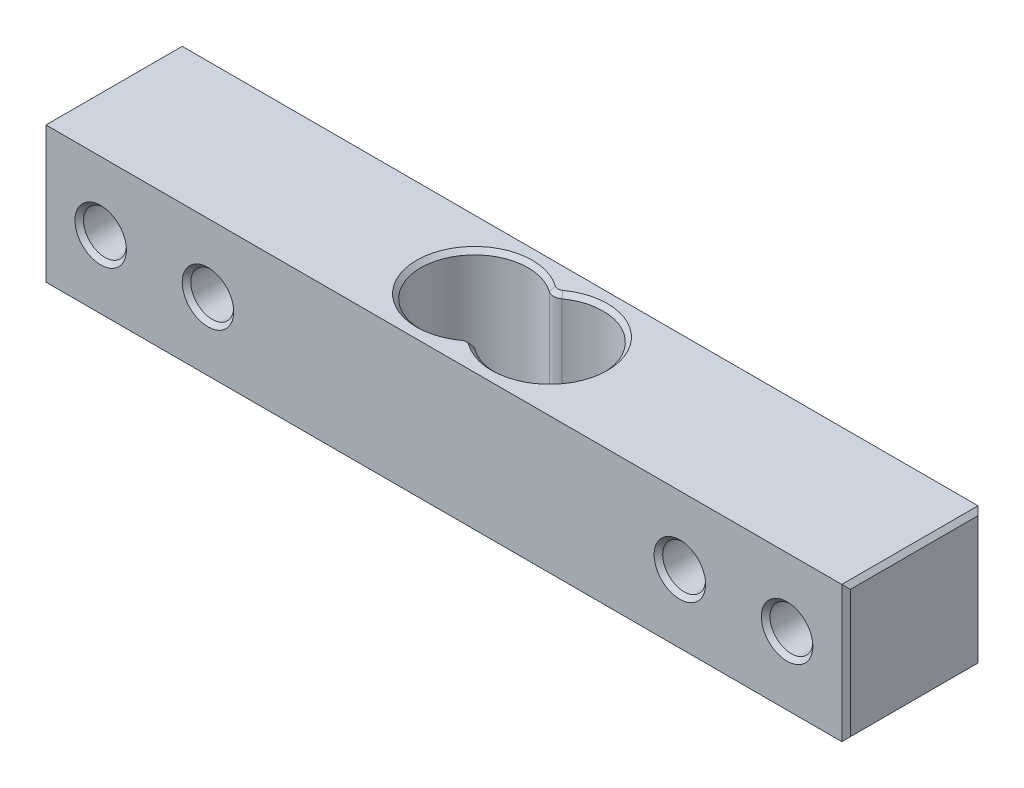
SolidWorks part; units mm, degrees
material "1060 Alloy"
ref_plane "Front Plane" through (0, 0, 0) normal (0, 0, 1) x (1, 0, 0)
ref_plane "Top Plane" through (0, 0, 0) normal (0, 1, 0) x (1, 0, 0)
ref_plane "Right Plane" through (0, 0, 0) normal (1, 0, 0) x (0, 0, -1)
sketch "Sketch1" plane through (0, 0, 0) normal (0, 0, 1) x (1, 0, 0)
  line L0 (-22, 0) -> (22, 0) construction
  line L1 (-37.5, -6.35) -> (37.5, -6.35)
  line L2 (-37.5, -6.35) -> (-37.5, 6.35)
  line L3 (-37.5, 6.35) -> (37.5, 6.35)
  line L4 (37.5, -6.35) -> (37.5, 6.35)
  line L5 (-37.5, -6.35) -> (37.5, 6.35) construction
  line L6 (-37.5, 6.35) -> (37.5, -6.35) construction
  circle A0 centre (-32, 0) radius 2
  circle A1 centre (-22, 0) radius 2
  circle A2 centre (22, 0) radius 2
  circle A3 centre (32, 0) radius 2
  point P0 (0, 0)
  point P14 (0, 0)
  dimension "D6" = 4
  dimension "D1" = 12.7
  dimension "D2" = 75
  dimension "D3" = 10
  dimension "D4" = 10
  dimension "D5" = 44
extrude "Boss-Extrude1" add sketch "Sketch1" along normal blind 12.7
sketch "Sketch2" plane through (0, 6.35, 0) normal (0, 1, 0) x (1, 0, 0)
  line L0 (-3.5, -6.35) -> (3.5, -6.35) construction
  line L1 (-37.5, -12.7) -> (-37.5, 0) construction
  arc A0 (0, -2.7793) -> (0, -9.9207) centre (-3.5, -6.35) ccw
  arc A1 (0, -9.9207) -> (0, -2.7793) centre (3.5, -6.35) ccw
  arc A2 (1.5, -6.35) -> (0, -2.7793) centre (-3.5, -6.35) ccw construction
  arc A3 (0, -2.7793) -> (-1.5, -6.35) centre (3.5, -6.35) ccw construction
  arc A4 (0, -9.9207) -> (1.5, -6.35) centre (-3.5, -6.35) ccw construction
  arc A5 (-1.5, -6.35) -> (0, -9.9207) centre (3.5, -6.35) ccw construction
  point P4 (0, -6.35)
  point P5 (-3.5, -8.4109)
  point P9 (-37.5, -6.35)
  dimension "D1" = 7
  dimension "D2" = 10
extrude "Cut-Extrude1" cut sketch "Sketch2" against normal up to next
fillet "Fillet1" radius 1 2 edges at (0, 0, 9.9207) (0, 0, 2.7793)
chamfer "Chamfer1" distance 0.4 angle 45 24 edges at (8.5, -6.35, 6.35) (0, -6.35, 10.2234) (0, -6.35, 2.4766) (-8.5, -6.35, 6.35) (8.5, 6.35, 6.35) (0, 6.35, 2.4766) (0, 6.35, 10.2234) (-8.5, 6.35, 6.35) (-37.5, 6.35, 6.35) (-37.5, 0, 12.7) (-37.5, -6.35, 6.35) (-37.5, 0, 0) (37.5, -6.35, 6.35) (37.5, 0, 12.7) (37.5, 6.35, 6.35) (37.5, 0, 0) (34, 0, 0) (34, 0, 12.7) (24, 0, 0) (24, 0, 12.7) (-20, 0, 0) (-20, 0, 12.7) (-30, 0, 0) (-30, 0, 12.7)
ref_point "Point2"
ref_point "Point4"
ref_axis "Axis1" through (-37.5, 0, 6.35) along (1, 0, 0)
